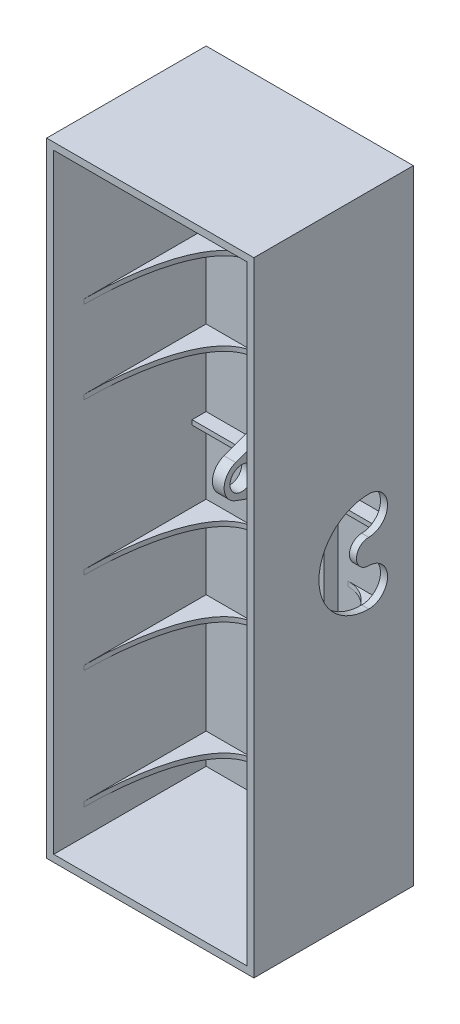
SolidWorks part; units mm, degrees
ref_plane "Front Plane" through (0, 0, 0) normal (0, 0, 1) x (1, 0, 0)
ref_plane "Top Plane" through (0, 0, 0) normal (0, 1, 0) x (1, 0, 0)
ref_plane "Right Plane" through (0, 0, 0) normal (1, 0, 0) x (0, 0, -1)
sketch "Sketch1" plane through (0, 0, 0) normal (0, 0, 1) x (1, 0, 0)
  line L0 (0, 263) -> (0, 0)
  line L1 (0, 0) -> (88.35, 0)
  line L3 (3, 3) -> (85.35, 3)
  line L7 (0, 263) -> (3, 263)
  line L8 (3, 3) -> (3, 263)
  line L11 (85.35, 3) -> (85.35, 263.0928)
  line L12 (85.35, 263.0928) -> (88.35, 263.0928)
  line L13 (88.35, 0) -> (88.35, 263.0928)
  dimension "D1" = 3
  dimension "D2" = 3
  dimension "D3" = 260
  dimension "D4" = 82.35
  dimension "D5" = 3
extrude "Boss-Extrude1" add sketch "Sketch1" along normal blind 68
sketch "Sketch2" plane through (0, 0, 0) normal (0, 0, 1) x (1, 0, 0)
  line L1 (0, 263) -> (88.35, 263)
  line L2 (0, 263) -> (0, 0)
  line L3 (0, 0) -> (88.35, 0)
  line L4 (88.35, 263) -> (88.35, 0)
extrude "Boss-Extrude2" add sketch "Sketch2" along normal blind 3
ref_plane "Plane1" through (34.175, 0, 0) normal (1, 0, 0) x (0, 0, -1)
sketch "Sketch3" plane through (34.175, 0, 0) normal (1, 0, 0) x (0, 0, -1)
  line L2 (-21.5652, 140.0477) -> (-3, 146.8049)
  line L3 (-3, 3) -> (-3, 263) construction
  line L4 (-3, 146.8049) -> (-3, 119.1951)
  line L5 (-3, 119.1951) -> (-21.5652, 125.9523)
  line L7 (-68, 3) -> (-3, 3) construction
  arc A0 (-21.5652, 140.0477) -> (-21.5652, 125.9523) centre (-19, 133) ccw
  circle A1 centre (-19, 133) radius 5
  dimension "D2" = 15
  dimension "D5" = 10
  dimension "D1" = 16
  dimension "D3" = 130
  dimension "D4" = 70
extrude "Boss-Extrude3" add sketch "Sketch3" against normal blind 5
ref_plane "Plane2" through (54.175, 0, 0) normal (1, 0, 0) x (0, 0, -1)
sketch "Sketch6" plane through (54.175, 0, 0) normal (1, 0, 0) x (0, 0, -1)
  line L0 (-19, 138) -> (-3, 138)
  line L2 (-3, 138) -> (-3, 128)
  line L3 (-3, 128) -> (-19, 128)
  line L4 (-3, 263) -> (-3, 3) construction
  arc A0 (-19, 138) -> (-19, 128) centre (-19, 133) ccw
  circle A1 centre (-19, 133) radius 5 construction
extrude "Boss-Extrude6" add sketch "Sketch6" along normal blind 8
hole_wizard "M6 Tapped Hole1" positions "Sketch7" profile "Sketch8" tap size "M6" standard "ISO" end condition up to next
sketch "Sketch7" plane through (54.175, 0, 0) normal (-1, 0, 0) x (0, 0, 1)
  arc A0 (19, 128) -> (19, 138) centre (19, 133) ccw construction
  point P0 (19, 133)
sketch "Sketch8" plane through (54.175, 133, 19) normal (0, 1, 0) x (0, 0, 1)
  line L0 (0, 0) -> (0, 8)
  line L1 (0, 8) -> (2.5, 8)
  line L2 (2.5, 8) -> (2.5, 0)
  line L5 (2.5, 0) -> (0, 0)
  line L11 (0, -6.35) -> (0, 107.95) construction
  dimension "Thread Major Dia." = 5
  dimension "Thru Tap Drill Depth" = 8
sketch "Sketch10" plane through (85.35, 0, 0) normal (-1, 0, 0) x (0, 0, 1)
  line L2 (3, 263) -> (3, 3) construction
  line L4 (19, 146.25) -> (19, 119.75) construction
  arc A0 (19, 146.25) -> (19, 119.75) centre (19, 133) cw construction
  arc A1 (19, 111.75) -> (19, 154.25) centre (19, 133) ccw
  arc A2 (19, 127.75) -> (19, 138.25) centre (19, 133) ccw
  arc A3 (19, 127.75) -> (19, 111.75) centre (19, 119.75) ccw
  arc A4 (19, 154.25) -> (19, 138.25) centre (19, 146.25) ccw
  point P5 (32.25, 133)
  point P20 (3, 133)
  dimension "D3" = 8
  dimension "D1" = 16
  dimension "D2" = 13.25
extrude "Cut-Extrude1" cut sketch "Sketch10" against normal up to next
sketch "Sketch11" plane through (0, 263, 0) normal (0, 1, 0) x (1, 0, 0)
  line L4 (0, 0) -> (0, -68)
  line L5 (88.35, 0) -> (0, 0)
  line L6 (88.35, -68) -> (88.35, 0)
  line L7 (0, -68) -> (88.35, -68)
  line L8 (0, 0) -> (0, -68)
  line L9 (88.35, 0) -> (0, 0)
  line L10 (88.35, -68) -> (88.35, 0)
  line L11 (0, -68) -> (88.35, -68)
  dimension "D1" = 0
extrude "Boss-Extrude7" add sketch "Sketch11" along normal blind 3
ref_plane "Plane4" through (44.175, 0, 0) normal (1, 0, 0) x (0, 0, -1)
sketch "Sketch13" plane through (0, 0, 3) normal (0, 0, 1) x (1, 0, 0)
  line L0 (3, 3) -> (3, 263) construction
  line L1 (3, 251.9797) -> (24.8525, 251.9797)
  line L2 (3, 251.9797) -> (3, 249.9797)
  line L3 (3, 249.9797) -> (24.8525, 249.9797)
  line L4 (24.8525, 251.9797) -> (24.8525, 249.9797)
  line L5 (3, 3) -> (3, 263) construction
  line L6 (3, 201.6285) -> (24.8525, 201.6285)
  line L7 (3, 201.6285) -> (3, 199.6285)
  line L8 (3, 199.6285) -> (24.8525, 199.6285)
  line L9 (24.8525, 201.6285) -> (24.8525, 199.6285)
  line L10 (3, 166.3498) -> (24.8525, 166.3498)
  line L11 (3, 166.3498) -> (3, 164.3498)
  line L12 (3, 164.3498) -> (24.8525, 164.3498)
  line L13 (24.8525, 166.3498) -> (24.8525, 164.3498)
  line L14 (3, 133) -> (85.35, 133) construction
  line L15 (85.35, 263) -> (85.35, 3) construction
  line L16 (3, 16.0203) -> (24.8525, 16.0203)
  line L17 (24.8525, 14.0203) -> (24.8525, 16.0203)
  line L18 (3, 14.0203) -> (24.8525, 14.0203)
  line L19 (3, 14.0203) -> (3, 16.0203)
  line L20 (3, 66.3715) -> (24.8525, 66.3715)
  line L21 (24.8525, 64.3715) -> (24.8525, 66.3715)
  line L22 (3, 64.3715) -> (24.8525, 64.3715)
  line L23 (3, 64.3715) -> (3, 66.3715)
  line L24 (3, 101.6502) -> (24.8525, 101.6502)
  line L25 (24.8525, 99.6502) -> (24.8525, 101.6502)
  line L26 (3, 99.6502) -> (24.8525, 99.6502)
  line L27 (3, 99.6502) -> (3, 101.6502)
  dimension "D1" = 2
extrude "Boss-Extrude8" add sketch "Sketch13" along normal blind 52
sketch "Sketch14" plane through (0, 14.0203, 0) normal (0, -1, 0) x (1, 0, 0)
  line L0 (3, 3) -> (24.8525, 3) construction
  line L1 (3, 55) -> (3, 3) construction
  line L2 (24.8525, 3) -> (24.8525, 55)
  line L3 (24.8525, 55) -> (3, 55)
  spline S0 degree 3 poles (3, 55) (3, 38.0721) (6.2716, 3) (24.8525, 3) knots 0 0 0 0 1 1 1 1
extrude "Cut-Extrude2" cut sketch "Sketch14" against normal up to surface (237.9595 mm away) up to face at (13.9263, 251.9797, 29)
mirror "Mirror3" about plane through (44.175, 0, 0) normal (1, 0, 0) of "Boss-Extrude8", "Cut-Extrude2"
sketch "Sketch15" plane through (0, 0, 3) normal (0, 0, 1) x (1, 0, 0)
  line L0 (85.35, 263) -> (3, 263) construction
  line L1 (30.675, 263) -> (32.675, 263)
  line L2 (30.675, 263) -> (30.675, 3)
  line L3 (30.675, 3) -> (32.675, 3)
  line L4 (32.675, 263) -> (32.675, 3)
  line L5 (85.35, 3) -> (3, 3) construction
  line L6 (29.175, 119.1951) -> (34.175, 119.1951) construction
  line L7 (3, 263) -> (85.35, 263) construction
  line L8 (59.175, 263) -> (57.175, 263)
  line L9 (59.175, 263) -> (59.175, 3)
  line L10 (59.175, 3) -> (57.175, 3)
  line L11 (57.175, 263) -> (57.175, 3)
  line L12 (62.175, 128) -> (54.175, 128) construction
  line L13 (29.175, 119.1951) -> (29.175, 146.8049) construction
  line L14 (29.175, 134) -> (3, 134)
  line L15 (29.175, 134) -> (29.175, 132)
  line L16 (29.175, 132) -> (3, 132)
  line L17 (3, 134) -> (3, 132)
  line L18 (3, 101.6502) -> (3, 164.3498) construction
  line L19 (62.175, 128) -> (62.175, 138) construction
  line L20 (62.175, 134) -> (85.35, 134)
  line L21 (62.175, 134) -> (62.175, 132)
  line L22 (62.175, 132) -> (85.35, 132)
  line L23 (85.35, 134) -> (85.35, 132)
  line L24 (85.35, 263) -> (85.35, 3) construction
  line L25 (29.175, 140.0477) -> (29.175, 125.9523) construction
  point P10 (31.675, 119.1951)
  point P11 (31.675, 3)
  point P18 (58.175, 3)
  point P21 (58.175, 128)
  point P38 (62.175, 133)
  point P39 (29.175, 133)
  dimension "D1" = 2
extrude "Boss-Extrude9" add sketch "Sketch15" along normal blind 6
sketch "Sketch16" plane through (0, 0, 3) normal (0, 0, 1) x (1, 0, 0)
  line L1 (36.675, 258) -> (51.675, 258)
  line L2 (36.675, 258) -> (36.675, 208)
  line L3 (36.675, 208) -> (51.675, 208)
  line L4 (51.675, 258) -> (51.675, 208)
  line L5 (54.175, 138) -> (54.175, 128) construction
  line L7 (34.175, 133) -> (54.175, 133) construction
  line L8 (34.175, 119.1951) -> (34.175, 146.8049) construction
  line L9 (36.675, 58) -> (51.675, 58)
  line L10 (51.675, 8) -> (51.675, 58)
  line L11 (36.675, 8) -> (51.675, 8)
  line L12 (36.675, 8) -> (36.675, 58)
  line L13 (88.35, 266) -> (0, 266) construction
  point P10 (54.175, 133)
  point P11 (51.675, 233)
  point P20 (44.175, 266)
  point P21 (44.175, 258)
  dimension "D1" = 15
  dimension "D2" = 50
  dimension "D3" = 100
extrude "Boss-Extrude10" add sketch "Sketch16" along normal blind 4
hole_wizard "M6 Tapped Hole2" positions "Sketch17" profile "Sketch18" tap size "M6" standard "ISO" end condition up to next
sketch "Sketch17" plane through (0, 0, 7) normal (0, 0, 1) x (1, 0, 0)
  line L0 (51.675, 258) -> (36.675, 258) construction
  line L1 (36.675, 208) -> (51.675, 208) construction
  line L2 (51.675, 58) -> (36.675, 58) construction
  line L3 (36.675, 8) -> (51.675, 8) construction
  point P0 (44.175, 250.24)
  point P2 (44.175, 215.76)
  point P4 (44.175, 50.24)
  point P6 (44.175, 15.76)
  point P18 (44.175, 8)
  dimension "D1" = 7.76
  dimension "D2" = 7.76
  dimension "D3" = 7.76
  dimension "D4" = 7.76
sketch "Sketch18" plane through (44.175, 250.24, 7) normal (1, 0, 0) x (0, -1, 0)
  line L0 (0, 0) -> (0, 7)
  line L1 (0, 7) -> (2.5, 7)
  line L2 (2.5, 7) -> (2.5, 0)
  line L5 (2.5, 0) -> (0, 0)
  line L11 (0, -6.35) -> (0, 107.95) construction
  dimension "Thru Tap Drill Dia." = 5
  dimension "Thru Tap Drill Depth" = 7
cosmetic thread "Hole Thread2" parameters "D2"=6
cosmetic thread "Hole Thread3" parameters "D2"=6
cosmetic thread "Hole Thread4" parameters "D2"=6
cosmetic thread "Hole Thread5" parameters "D2"=6
